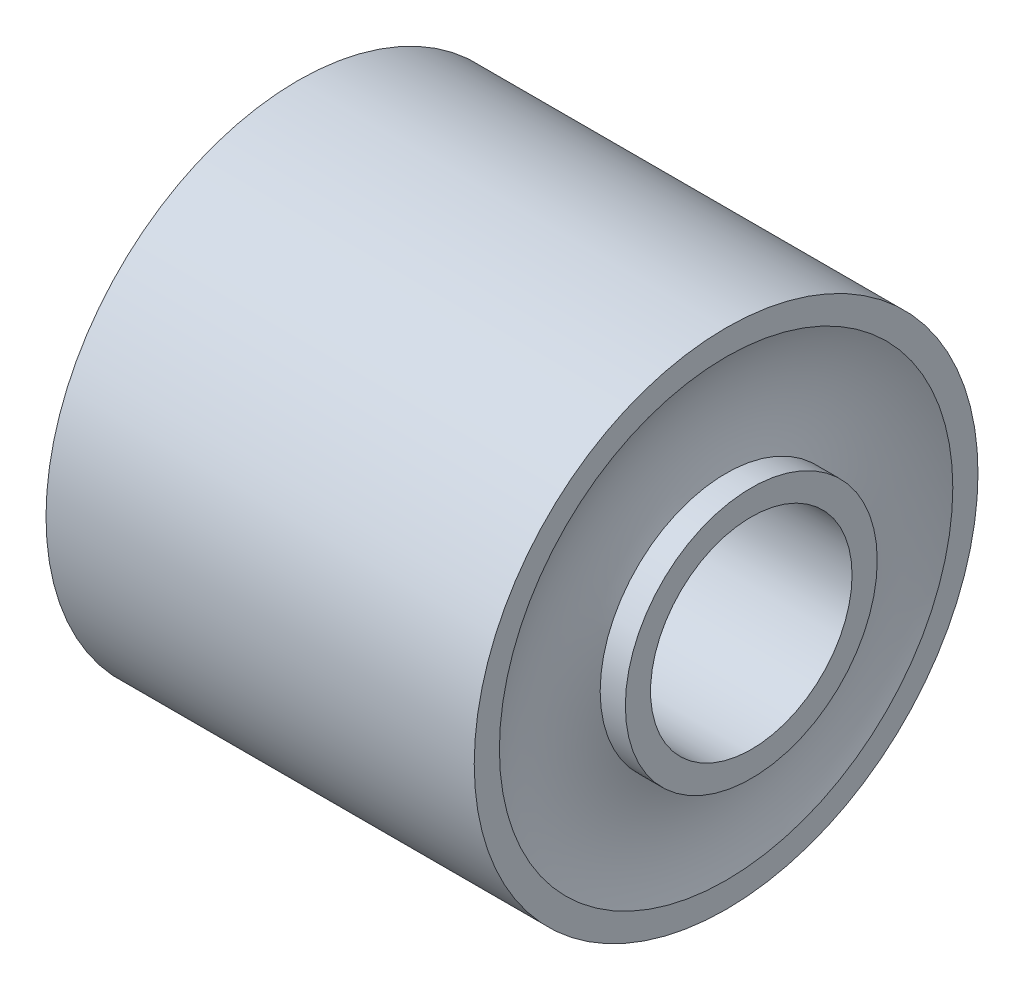
SolidWorks part; units mm, degrees
material "S235JR (1.0037)"
ref_plane "Płaszczyzna przednia" through (0, 0, 0) normal (0, 0, 1) x (1, 0, 0)
ref_plane "Płaszczyzna górna" through (0, 0, 0) normal (0, 1, 0) x (1, 0, 0)
ref_plane "Płaszczyzna prawa" through (0, 0, 0) normal (1, 0, 0) x (0, 0, -1)
sketch "Szkic1" plane through (0, 0, 0) normal (1, 0, 0) x (0, 0, -1)
  circle A0 centre (0, 0) radius 5
  circle A1 centre (0, 0) radius 4
  dimension "D1" = 8
  dimension "D2" = 1
extrude "Dodanie-wyciągnięcie1" add sketch "Szkic1" along normal mid plane 19
sketch "Szkic2" plane through (0, 0, 0) normal (1, 0, 0) x (0, 0, -1)
  circle A0 centre (0, 0) radius 9
  circle A1 centre (0, 0) radius 10
  dimension "D1" = 20
  dimension "D2" = 1
extrude "Dodanie-wyciągnięcie2" add sketch "Szkic2" along normal mid plane 17 separate body
sketch "Szkic3" plane through (0, 0, 0) normal (0, 0, 1) x (1, 0, 0)
  line L0 (-9.5, 0) -> (9.5, 0) construction
  line L1 (-9.5, 4) -> (-9.5, -4) construction
  line L2 (9.5, -4) -> (9.5, 4) construction
  line L3 (-8.5, 9) -> (8.5, 9)
  line L4 (-8.5, 9) -> (-8.5, -9) construction
  line L5 (-8.5, 10) -> (-8.5, -10) construction
  line L6 (8.5, -9) -> (8.5, 9) construction
  line L7 (8.5, -10) -> (8.5, 10) construction
  line L8 (9.5, 5) -> (-9.5, 5) construction
  line L9 (-8.5, 5) -> (8.5, 5)
  arc A0 (-8.5, 9) -> (-8.5, 5) centre (-13.0826, 7) cw
  arc A1 (8.5, 9) -> (8.5, 5) centre (13.0826, 7) ccw
  dimension "D1" = 5
revolve "Obrót1" add sketch "Szkic3" angle 360 about L0
